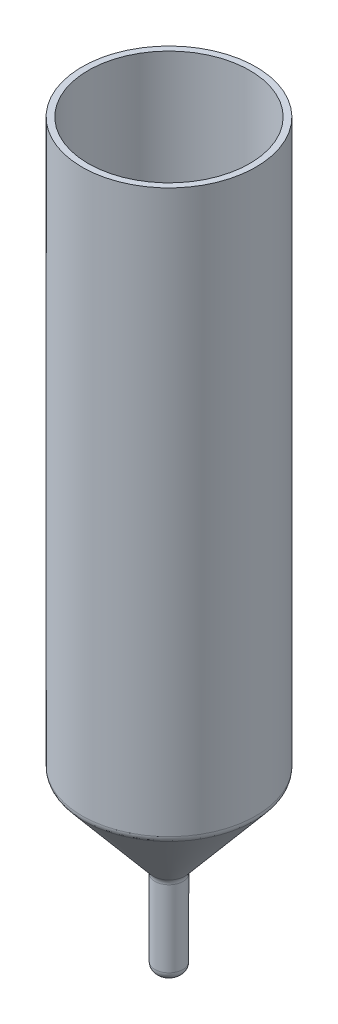
SolidWorks part; units mm, degrees
ref_plane "Front Plane" through (0, 0, 0) normal (0, 0, 1) x (1, 0, 0)
ref_plane "Top Plane" through (0, 0, 0) normal (0, 1, 0) x (1, 0, 0)
ref_plane "Right Plane" through (0, 0, 0) normal (1, 0, 0) x (0, 0, -1)
sketch "Sketch1" plane through (0, 0, 0) normal (0, 0, 1) x (1, 0, 0)
  line L0 (0, 0) -> (0, -41.9289) construction
  line L1 (-18.5816, 0) -> (-18.5816, -129.4837)
  line L2 (-18.5816, -129.4837) -> (-2.218, -148.9851)
  line L4 (-20, 0) -> (-20, -130)
  line L5 (-20, -130) -> (-3.218, -150)
  line L7 (-20, 0) -> (-18.5816, 0)
  line L9 (-3.218, -150) -> (-3.218, -170)
  line L10 (-3.218, -150) -> (21.8625, -170.4213) construction
  line L11 (-2.218, -148.9851) -> (22.7581, -169.3214) construction
  line L12 (-2.218, -148.9851) -> (-2.218, -170.0005)
  line L13 (-2.218, -170.0005) -> (-3.218, -170)
  dimension "D1" = 130
  dimension "D2" = 20
  dimension "D3" = 21.0154
  dimension "D4" = 20
  dimension "D5" = 1
  dimension "D6" = 20
  dimension "D7" = 140
  dimension "D8" = 1.4184
  dimension "D9" = 0
  dimension "D10" = 2.218
revolve "Revolve1" add sketch "Sketch1" angle 360 about L0
fillet "Fillet1" radius 2 1 edges at (0, -130, 20)
fillet "Fillet2" radius 2 2 edges at (0, -170, 3.218) (0, -150, 3.218)
